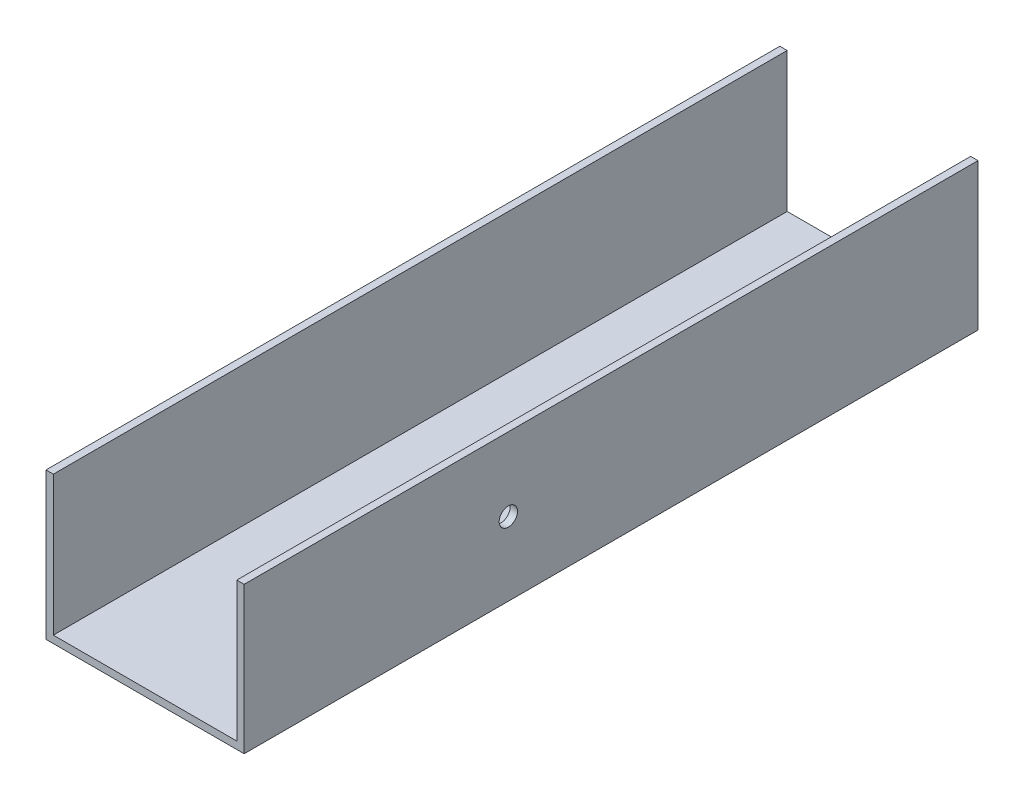
SolidWorks part; units mm, degrees
ref_plane "Alzado" through (0, 0, 0) normal (0, 0, 1) x (1, 0, 0)
ref_plane "Planta" through (0, 0, 0) normal (0, 1, 0) x (1, 0, 0)
ref_plane "Vista lateral" through (0, 0, 0) normal (1, 0, 0) x (0, 0, -1)
sketch "Croquis1" plane through (0, 0, 0) normal (0, 0, 1) x (1, 0, 0)
  line L0 (0, 22.9641) -> (0, -26.2672) construction
  line L1 (-27, -20) -> (27, -20) construction
  line L2 (-27, -20) -> (-27, 20) construction
  line L3 (-27, 20) -> (27, 20) construction
  line L4 (27, -20) -> (27, 20) construction
  line L5 (-27, -20) -> (27, 20) construction
  line L6 (-27, 20) -> (27, -20) construction
  line L7 (-27, 20) -> (-27, -20)
  line L8 (-27, -20) -> (27, -20)
  line L9 (0, -20) -> (0, -18)
  line L10 (25, -18) -> (-25, -18)
  line L11 (-25, -18) -> (-25, 20)
  line L12 (-25, 20) -> (-27, 20)
  line L13 (25, -18) -> (25, 20)
  line L14 (27, 20) -> (27, -20)
  line L15 (25, 20) -> (27, 20)
  point P0 (0, 0)
  dimension "D1" = 40
  dimension "D2" = 54
  dimension "D3" = 2
  dimension "D4" = 2
extrude "Saliente-Extruir1" add sketch "Croquis1" along normal mid plane 200 contours L11 L12 L7 L8 L9 L10 | L10 L11 L12 L7 L8 L14 L15 L13 region at (-26, 19.5174, 0)
sketch "Croquis2" plane through (27, 0, 0) normal (1, 0, 0) x (0, 0, -1)
  line L0 (0, 0) -> (-56.8754, 0) construction
  circle A0 centre (-28, 0) radius 2.5
  point P2 (0, 0)
  dimension "D2" = 5
  dimension "D1" = 28
extrude "Cortar-Extruir1" cut sketch "Croquis2" against normal blind 10
